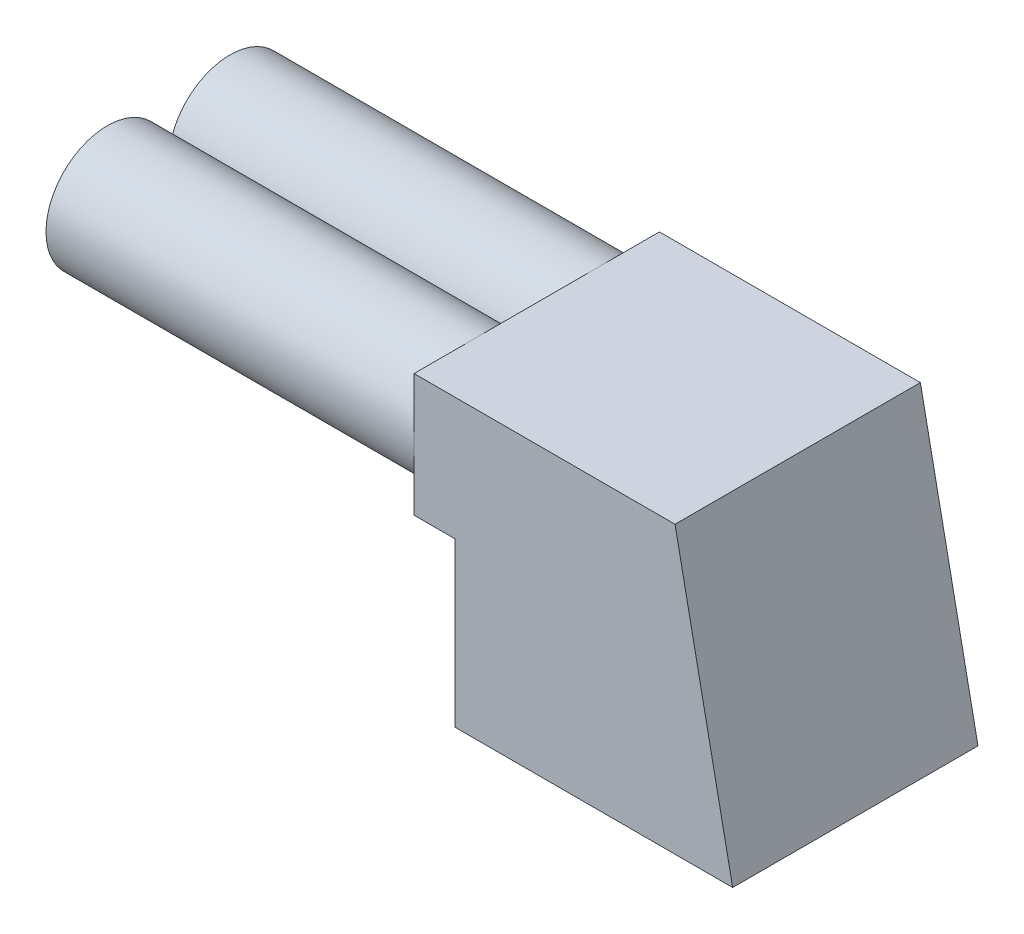
SolidWorks part; units mm, degrees
ref_plane "Piano frontale" through (0, 0, 0) normal (0, 0, 1) x (1, 0, 0)
ref_plane "Piano superiore" through (0, 0, 0) normal (0, 1, 0) x (1, 0, 0)
ref_plane "Piano destro" through (0, 0, 0) normal (1, 0, 0) x (0, 0, -1)
sketch "Schizzo2" plane through (0, 0, 0) normal (0, 0, 1) x (1, 0, 0)
  line L0 (-27.0558, 0) -> (40.8655, 0)
  line L1 (40.8655, 0) -> (26.7739, 69.894)
  line L2 (26.7739, 69.894) -> (-27.0558, 69.894)
  line L3 (-27.0558, 69.894) -> (-27.0558, 0)
extrude "Estrusione-Estrusione1" add sketch "Schizzo2" along normal blind 30 and the other way blind 30
sketch "Schizzo3" plane through (-27.0558, 0, 0) normal (-1, 0, 0) x (0, 0, 1)
  line L0 (-30, 54.894) -> (30, 54.894) construction
  line L1 (-30, 69.894) -> (-30, 0) construction
  line L2 (30, 69.894) -> (30, 0) construction
  line L3 (-30, 69.894) -> (30, 69.894) construction
  line L4 (-0.0137, 55.534) -> (0.0137, 55.534)
  line L5 (-0.022, 54.0821) -> (0.022, 54.0821)
  arc A0 (-0.0137, 55.534) -> (-0.022, 54.0821) centre (-15, 54.894) ccw
  arc A1 (0.022, 54.0821) -> (0.0137, 55.534) centre (15, 54.894) ccw
  dimension "D2" = 30
  dimension "D1" = 15
extrude "Estrusione-Estrusione2" add sketch "Schizzo3" along normal blind 100
sketch "Schizzo4" plane through (-27.0558, 0, 0) normal (-1, 0, 0) x (0, 0, 1)
  line L0 (30, 54.894) -> (30, 0) construction
  line L1 (-30, 69.894) -> (30, 69.894)
  line L2 (-30, 69.894) -> (-30, 39.894)
  line L3 (-30, 39.894) -> (30, 39.894)
  line L4 (30, 69.894) -> (30, 39.894)
  arc A0 (0.022, 54.0821) -> (30, 54.894) centre (15, 54.894) ccw construction
extrude "Estrusione-Estrusione3" add sketch "Schizzo4" along normal blind 10
